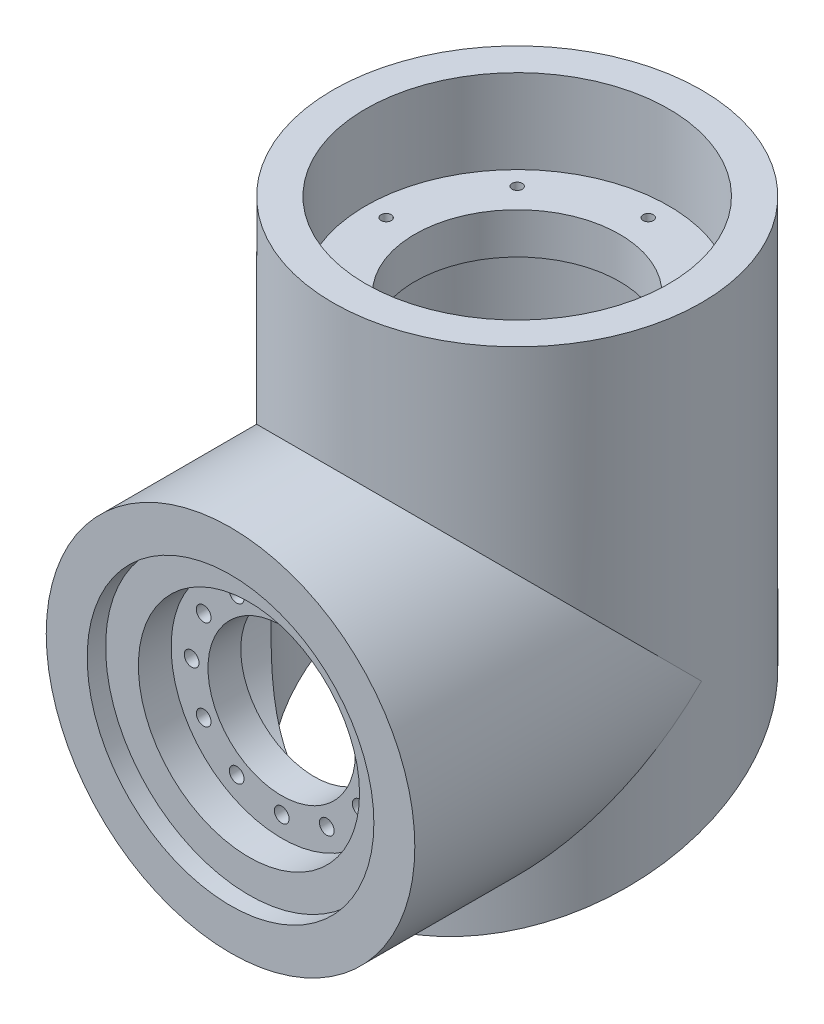
SolidWorks part; units mm, degrees
ref_plane "前视基准面" through (0, 0, 0) normal (0, 0, 1) x (1, 0, 0)
ref_plane "上视基准面" through (0, 0, 0) normal (0, 1, 0) x (1, 0, 0)
ref_plane "右视基准面" through (0, 0, 0) normal (1, 0, 0) x (0, 0, -1)
sketch "草图1" plane through (0, 0, 0) normal (0, 0, 1) x (1, 0, 0)
  circle A0 centre (0, 0) radius 45
  dimension "D1" = 90
extrude "凸台-拉伸1" add sketch "草图1" along normal blind 70
sketch "草图2" plane through (0, 0, 0) normal (0, 1, 0) x (1, 0, 0)
  circle A0 centre (0, 0) radius 45
extrude "凸台-拉伸2" add sketch "草图2" along normal blind 80 and the other way blind 48
sketch "草图3" plane through (0, 80, 0) normal (0, 1, 0) x (1, 0, 0)
  circle A0 centre (0, 0) radius 37
  dimension "D1" = 74
extrude "切除-拉伸1" cut sketch "草图3" against normal blind 20.5 contours A0
sketch "草图5" plane through (0, -48, 0) normal (0, -1, 0) x (1, 0, 0)
  circle A0 centre (0, 0) radius 37.5
  dimension "D1" = 75
extrude "切除-拉伸2" cut sketch "草图5" against normal offset from surface (97.5 mm away) 10 contours A0 up to face at (0, 59.5, 37)
sketch "草图6" plane through (0, -48, 0) normal (0, -1, 0) x (1, 0, 0)
  circle A0 centre (0, 0) radius 42.5
  dimension "D1" = 85
extrude "切除-拉伸3" cut sketch "草图6" against normal offset from surface (39.9 mm away) 57.6 up to face at (0, 49.5, 37.5)
sketch "草图7" plane through (0, 59.5, 0) normal (0, 1, 0) x (1, 0, 0)
  circle A0 centre (0, 0) radius 25
  dimension "D1" = 50
extrude "切除-拉伸4" cut sketch "草图7" against normal through all
hole_wizard "M3 螺纹孔1" positions "草图9" profile "草图8" tap size "M3" standard "GB"
sketch "草图9" plane through (0, 59.5, 0) normal (0, 1, 0) x (1, 0, 0)
  line L0 (0, 0) -> (0, 47.6711) construction
  circle A0 centre (0, 0) radius 32 construction
  point P0 (0, 32)
  dimension "D1" = 64
sketch "草图8" plane through (0, 59.5, -32) normal (1, 0, 0) x (0, 0, 1)
  line L0 (0, 0) -> (0, 8.2511)
  line L1 (0, 8.2511) -> (1.25, 7.5)
  line L2 (1.25, 7.5) -> (1.25, 0)
  line L5 (1.25, 0) -> (0, 0)
  line L10 (0, 8.2511) -> (-1.25, 7.5) construction
  line L11 (0, -6.35) -> (0, 107.95) construction
  dimension "螺纹孔钻头直径" = 2.5
  dimension "螺纹孔钻头深度" = 7.5
  dimension "导头角度" = 118
cosmetic thread "孔螺蚊线1" parameters "D1"=6, "D2"=3
ref_axis "基准轴1" through (0, -48, 0) along (0, 1, 0)
pattern_circular "阵列(圆周)1" count 8 over 360 about axis through (0, -48, 0) along (0, 1, 0) of "M3 螺纹孔1"
sketch "草图11" plane through (0, 0, 70) normal (0, 0, 1) x (1, 0, 0)
  circle A0 centre (0, 0) radius 35
  dimension "D1" = 70
extrude "切除-拉伸6" cut sketch "草图11" against normal blind 4.5
sketch "草图12" plane through (0, 0, 65.5) normal (0, 0, 1) x (1, 0, 0)
  circle A0 centre (0, 0) radius 27
  dimension "D1" = 54
extrude "切除-拉伸7" cut sketch "草图12" against normal blind 8
sketch "草图13" plane through (0, 0, 57.5) normal (0, 0, 1) x (1, 0, 0)
  circle A0 centre (0, 0) radius 18
  dimension "D1" = 36
extrude "切除-拉伸8" cut sketch "草图13" against normal blind 8
ref_plane "基准面1" through (0, 0, 49.5) normal (0, 0, 1) x (1, 0, 0)
sketch "草图14" plane through (0, 0, 49.5) normal (0, 0, 1) x (1, 0, 0)
  circle A0 centre (0, 0) radius 32.5
  dimension "D1" = 65
extrude "切除-拉伸9" cut sketch "草图14" against normal blind 40
hole_wizard "打孔尺寸(%根据)内六角圆柱头螺钉的类型1" positions "草图16" profile "草图15" counterbore size "M3" standard "GB" end condition through all
sketch "草图16" plane through (0, 0, 49.5) normal (0, 0, -1) x (-1, 0, 0)
  line L0 (0, 0) -> (-31.2047, 0) construction
  circle A0 centre (0, 0) radius 22 construction
  point P0 (-22, 0)
  dimension "D1" = 44
sketch "草图15" plane through (22, 0, 49.5) normal (1, 0, 0) x (0, 1, 0)
  line L0 (0, 0) -> (0, 20.5)
  line L1 (0, 20.5) -> (1.8, 20.5)
  line L3 (1.8, 20.5) -> (1.8, 3.4)
  line L4 (1.8, 3.4) -> (3, 3.4)
  line L5 (3, 3.4) -> (3, 0)
  line L7 (3, 0) -> (0, 0)
  line L11 (0, -6.35) -> (0, 107.95) construction
  dimension "通孔孔直径" = 3.6
  dimension "通孔孔深度" = 20.5
  dimension "柱形沉头孔直径" = 6
  dimension "柱形沉头孔深度" = 3.4
ref_axis "基准轴2" through (0, 0, 70) along (0, 0, -1)
pattern_circular "阵列(圆周)2" count 12 over 360 about axis through (0, 0, 70) along (0, 0, -1) of "打孔尺寸(%根据)内六角圆柱头螺钉的类型1"
hole_wizard "M3 螺纹孔2" positions "草图18" profile "草图17" tap size "M3" standard "GB"
sketch "草图18" plane through (0, -8.1, 0) normal (0, -1, 0) x (-1, 0, 0)
  line L0 (0, 0) -> (0, 51.4103) construction
  circle A0 centre (0, 0) radius 39 construction
  point P0 (0, 39)
  dimension "D1" = 78
cosmetic thread "孔螺蚊线2" parameters "D2"=3
sketch "草图17" plane through (0, -8.1, -39) normal (1, 0, 0) x (0, 0, -1)
  line L0 (0, 0) -> (0, 7.2511)
  line L1 (0, 7.2511) -> (1.25, 6.5)
  line L2 (1.25, 6.5) -> (1.25, 0)
  line L5 (1.25, 0) -> (0, 0)
  line L10 (0, 7.2511) -> (-1.25, 6.5) construction
  line L11 (0, -6.35) -> (0, 107.95) construction
  dimension "螺纹孔钻头直径" = 2.5
  dimension "螺纹孔钻头深度" = 6.5
  dimension "导头角度" = 118
pattern_circular "阵列(圆周)4" count 5 every 30 about axis through (0, -48, 0) along (0, 1, 0) of "M3 螺纹孔2"
mirror "镜向1" about plane through (0, 0, 0) normal (1, 0, 0) of "阵列(圆周)4", "M3 螺纹孔2"
sketch "草图19" plane through (0, 0, 0) normal (1, 0, 0) x (0, 0, -1)
  line L0 (-45, -48) -> (45, -48)
  line L1 (45, -48) -> (45, -15.2427)
  line L2 (45, -48) -> (45, 80) construction
  line L3 (45, -15.2427) -> (-45, -48)
  dimension "D1" = 20
extrude "切除-拉伸10" cut sketch "草图19" against normal through all and the other way through all
ref_plane "基准面2" through (0, -48, 0) normal (0, 1, 0) x (1, 0, 0)
sketch "草图21" plane through (0, -48, 0) normal (0, 1, 0) x (1, 0, 0)
  line L0 (0, 0) -> (0, -73.3686) construction
  circle A0 centre (0, 0) radius 43.75 construction
  circle A1 centre (0, -43.75) radius 0.8
  dimension "D1" = 87.5
  dimension "D2" = 1.6
extrude "切除-拉伸11" cut sketch "草图21" along normal blind 6 contours A1
sketch "草图22" plane through (0, -48, 0) normal (0, 1, 0) x (1, 0, 0)
  line L0 (0, 0) -> (0, 49.1981) construction
  circle A0 centre (0, 0) radius 43.75 construction
  circle A1 centre (0, 43.75) radius 0.8
  dimension "D1" = 87.5
  dimension "D2" = 1.6
extrude "切除-拉伸12" cut sketch "草图22" along normal blind 38
sketch "草图23" plane through (0, -48, 0) normal (0, 1, 0) x (1, 0, 0)
  line L0 (-55.1654, 0) -> (58.0688, 0) construction
  circle A0 centre (0, 0) radius 43.75 construction
  circle A1 centre (-43.75, 0) radius 0.8
  circle A2 centre (43.75, 0) radius 0.8
  dimension "D1" = 87.5
  dimension "D2" = 1.6
  dimension "D3" = 1.6
extrude "切除-拉伸13" cut sketch "草图23" along normal blind 24
